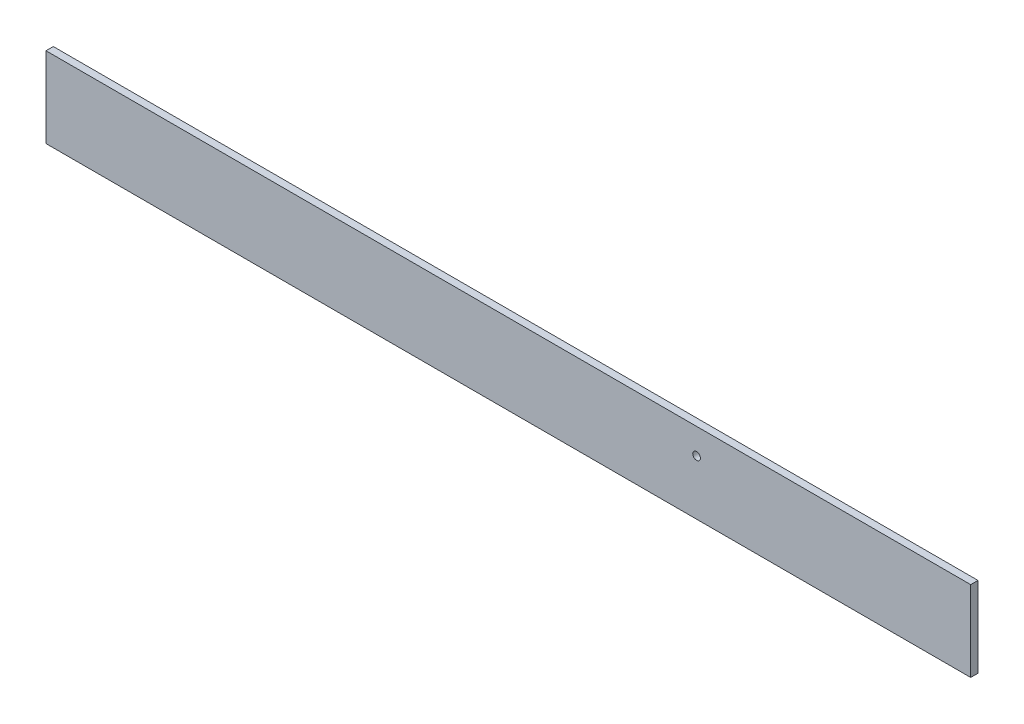
SolidWorks part; units mm, degrees
ref_plane "Front Plane" through (0, 0, 0) normal (0, 0, 1) x (1, 0, 0)
ref_plane "Top Plane" through (0, 0, 0) normal (0, 1, 0) x (1, 0, 0)
ref_plane "Right Plane" through (0, 0, 0) normal (1, 0, 0) x (0, 0, -1)
sketch "Sketch2" plane through (0, 0, 0) normal (0, 0, 1) x (1, 0, 0)
  line L1 (-253, -22) -> (253, -22)
  line L2 (-253, -22) -> (-253, 22)
  line L3 (-253, 22) -> (253, 22)
  line L4 (253, -22) -> (253, 22)
  line L5 (-253, -22) -> (253, 22) construction
  line L6 (-253, 22) -> (253, -22) construction
  circle A0 centre (103, 8) radius 2.1 construction
  circle A1 centre (103, 8) radius 2.1
  point P0 (0, 0)
  dimension "D1" = 44
  dimension "D2" = 506
extrude "Boss-Extrude1" add sketch "Sketch2" along normal blind 4
